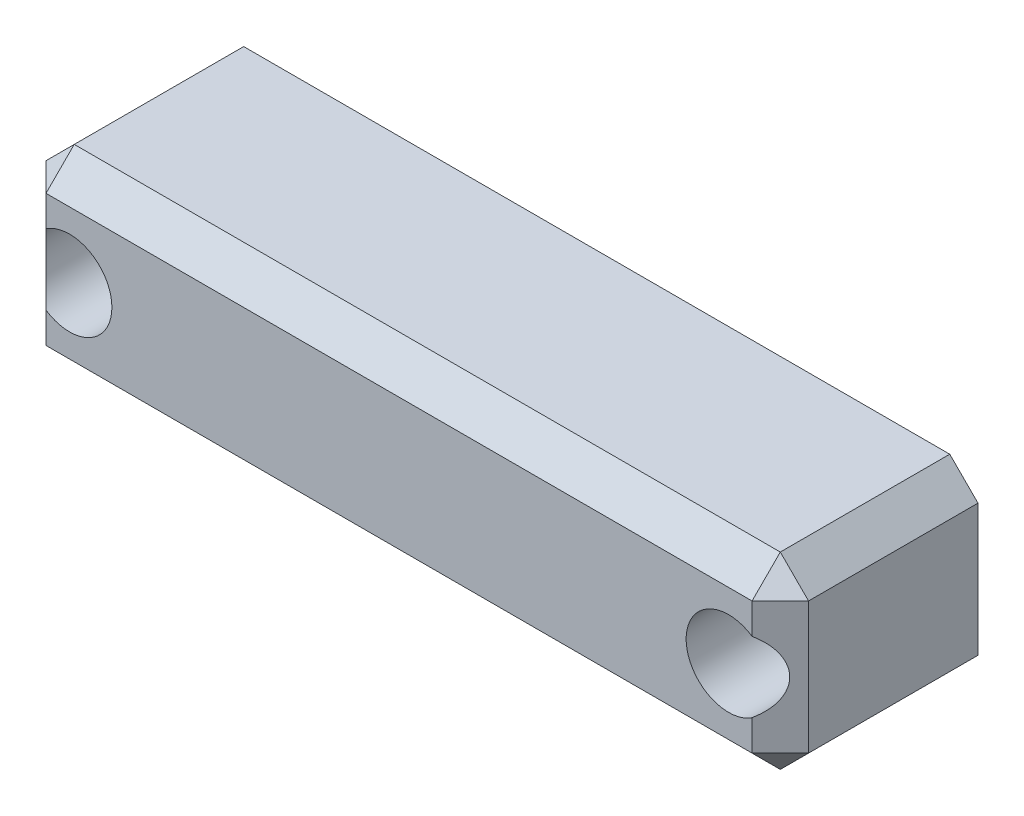
SolidWorks part; units mm, degrees
ref_plane "Front Plane" through (0, 0, 0) normal (0, 0, 1) x (1, 0, 0)
ref_plane "Top Plane" through (0, 0, 0) normal (0, 1, 0) x (1, 0, 0)
ref_plane "Right Plane" through (0, 0, 0) normal (1, 0, 0) x (0, 0, -1)
sketch "Sketch1" plane through (0, 0, 0) normal (0, 0, 1) x (1, 0, 0)
  line L0 (0, 0) -> (-35, 0) construction
  line L1 (-40.5, -10) -> (40.5, -10)
  line L2 (-40.5, -10) -> (-40.5, 10)
  line L3 (-40.5, 10) -> (40.5, 10)
  line L4 (40.5, -10) -> (40.5, 10)
  line L5 (-40.5, -10) -> (40.5, 10) construction
  line L6 (-40.5, 10) -> (40.5, -10) construction
  line L7 (0, 0) -> (0, 10) construction
  circle A0 centre (-35, 0) radius 1.6
  circle A1 centre (35, 0) radius 1.6
  point P0 (0, 0)
  dimension "D4" = 3.2
  dimension "D1" = 81
  dimension "D2" = 20
  dimension "D3" = 35
extrude "Boss-Extrude1" add sketch "Sketch1" along normal blind 2
sketch "Sketch2" plane through (0, 0, 2) normal (0, 0, 1) x (1, 0, 0)
  line L0 (-40.5, 10) -> (-40.5, -10) construction
  line L1 (-35, 3.2909) -> (-37.85, 1.6454)
  line L2 (-37.85, 1.6454) -> (-37.85, -1.6454)
  line L3 (-37.85, -1.6454) -> (-35, -3.2909)
  line L4 (-35, -3.2909) -> (-32.15, -1.6454)
  line L5 (-32.15, -1.6454) -> (-32.15, 1.6454)
  line L6 (-32.15, 1.6454) -> (-35, 3.2909)
  line L7 (0, 10) -> (0, 0) construction
  line L8 (40.5, 10) -> (-40.5, 10) construction
  line L9 (32.15, 1.6454) -> (35, 3.2909)
  line L10 (32.15, -1.6454) -> (32.15, 1.6454)
  line L11 (35, -3.2909) -> (32.15, -1.6454)
  line L12 (37.85, -1.6454) -> (35, -3.2909)
  line L13 (37.85, 1.6454) -> (37.85, -1.6454)
  line L14 (35, 3.2909) -> (37.85, 1.6454)
  line L16 (-40.5, 10) -> (40.5, 10)
  line L17 (-40.5, 10) -> (-40.5, -10)
  line L18 (-40.5, -10) -> (40.5, -10)
  line L19 (40.5, 10) -> (40.5, -10)
  circle A0 centre (-35, 0) radius 2.85 construction
  circle A1 centre (35, 0) radius 2.85 construction
  dimension "D1" = 0
  dimension "D2" = 5.7
extrude "Boss-Extrude2" add sketch "Sketch2" along normal blind 19
sketch "Sketch3" plane through (0, 0, 21) normal (0, 0, 1) x (1, 0, 0)
  circle A0 centre (-35, 0) radius 4.5
  circle A1 centre (35, 0) radius 4.5
  dimension "D1" = 9
  dimension "D2" = 9
extrude "Cut-Extrude1" cut sketch "Sketch3" against normal blind 16.5
sketch "Sketch4" plane through (0, -10, 0) normal (0, -1, 0) x (1, 0, 0)
  line L0 (-36, 5) -> (41.1829, 5) construction
  line L3 (-40.5, 21) -> (-40.5, 0) construction
  line L4 (-40.5, 21) -> (40.5, 21) construction
  text T0 "LIQUID" font "BankGothic Lt BT" height in points 36
  dimension "D1" = 4.5
  dimension "D2" = 16
extrude "Cut-Extrude2" cut sketch "Sketch4" against normal blind 0.6
sketch "Sketch5" plane through (0, 0, 0) normal (0, 0, -1) x (-1, 0, 0)
  line L0 (0, -10) -> (0, 10) construction
  line L1 (40.5, -10) -> (-40.5, -10) construction
  line L2 (-40.5, 10) -> (40.5, 10) construction
  line L4 (-24.2, -9) -> (-16, -9)
  line L5 (-24.2, -9) -> (-24.2, -5.8)
  line L6 (-24.2, -5.8) -> (-16, -5.8)
  line L7 (-16, -9) -> (-16, -5.8)
  line L8 (16, -9) -> (24.2, -9)
  line L9 (16, -9) -> (16, -5.8)
  line L10 (16, -5.8) -> (24.2, -5.8)
  line L11 (24.2, -9) -> (24.2, -5.8)
  dimension "D1" = 3.2
  dimension "D2" = 8.2
  dimension "D3" = 8.2
  dimension "D4" = 3.2
  dimension "D5" = 1
  dimension "D6" = 1
  dimension "D7" = 16
  dimension "D8" = 16
extrude "Cut-Extrude3" cut sketch "Sketch5" against normal blind 15
chamfer "Chamfer1" distance 3 angle 45 8 edges at (40.5, -10, 10.5) (40.5, 0, 21) (0, -10, 21) (-40.5, -10, 10.5) (-40.5, 0, 21) (-40.5, 10, 10.5) (40.5, 10, 10.5) (0, 10, 21)
